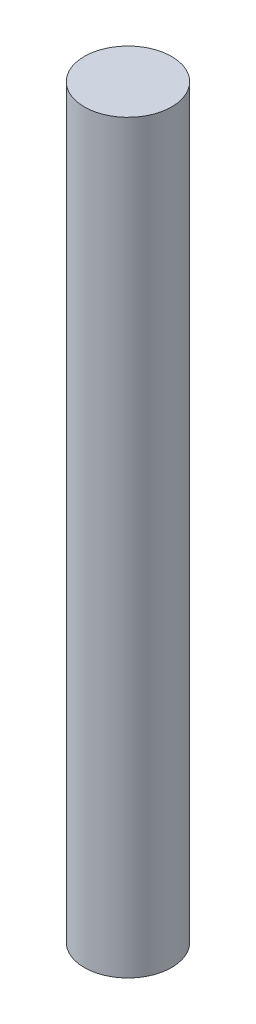
SolidWorks part; units mm, degrees
ref_plane "Front Plane" through (0, 0, 0) normal (0, 0, 1) x (1, 0, 0)
ref_plane "Top Plane" through (0, 0, 0) normal (0, 1, 0) x (1, 0, 0)
ref_plane "Right Plane" through (0, 0, 0) normal (1, 0, 0) x (0, 0, -1)
sketch "Sketch1" plane through (0, 0, 0) normal (0, 1, 0) x (1, 0, 0)
  circle A0 centre (0, 0) radius 3.9688
  dimension "D1" = 7.9375
extrude "Boss-Extrude1" add sketch "Sketch1" along normal blind 67.7333
scale "Scale1" scale about centroid uniform scaling yes scale factor 0.75
